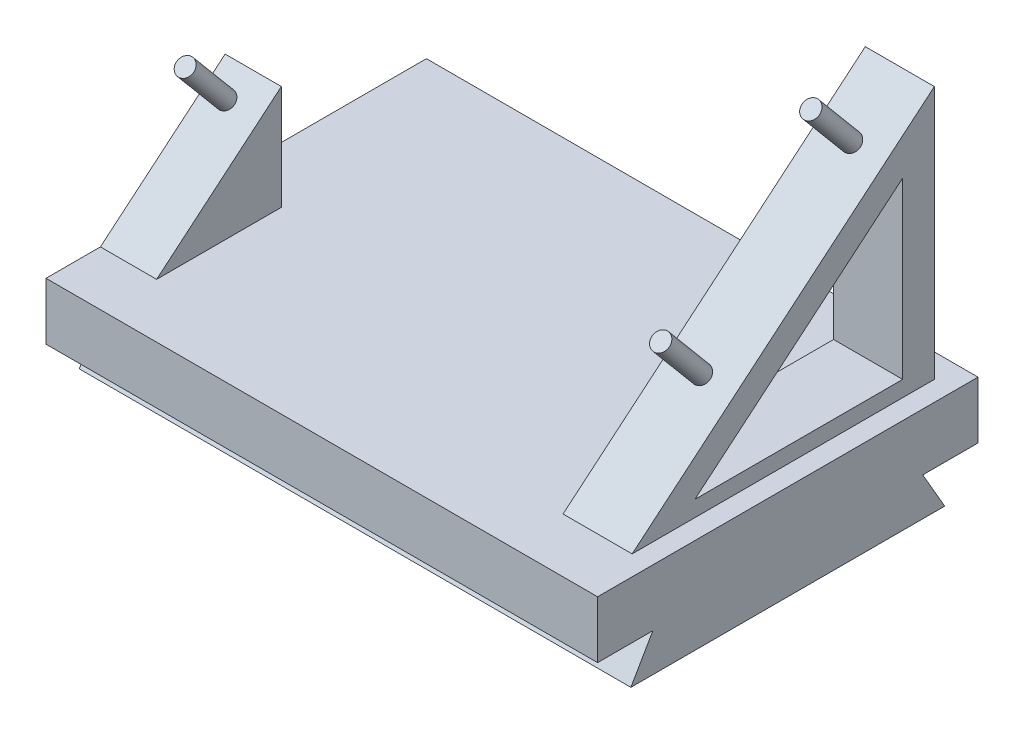
SolidWorks part; units mm, degrees
material "Plain Carbon Steel"
ref_plane "Front Plane" through (0, 0, 0) normal (0, 0, 1) x (1, 0, 0)
ref_plane "Top Plane" through (0, 0, 0) normal (0, 1, 0) x (1, 0, 0)
ref_plane "Right Plane" through (0, 0, 0) normal (1, 0, 0) x (0, 0, -1)
sketch "Sketch1" plane through (0, 0, 0) normal (0, 1, 0) x (1, 0, 0)
  line L1 (0, 0) -> (196, 0)
  line L2 (0, 0) -> (0, 150)
  line L3 (0, 150) -> (196, 150)
  line L4 (196, 0) -> (196, 150)
  dimension "D1" = 196
  dimension "D2" = 150
extrude "Boss-Extrude1" add sketch "Sketch1" along normal blind 15
sketch "Sketch2" plane through (0, 15, 0) normal (0, 1, 0) x (1, 0, 0)
  line L1 (15, 70) -> (181, 70)
  line L2 (15, 70) -> (15, 15)
  line L3 (15, 15) -> (181, 15)
  line L4 (181, 70) -> (181, 15)
  line L5 (0, 150) -> (0, 0) construction
  line L6 (0, 0) -> (196, 0) construction
  dimension "D1" = 166
  dimension "D2" = 15
  dimension "D3" = 15
  dimension "D4" = 55
extrude "Cut-Extrude1" cut sketch "Sketch2" against normal blind 9.68
sketch "Sketch3" plane through (0, 15, 0) normal (0, 1, 0) x (1, 0, 0)
  line L0 (0, 150) -> (0, 0) construction
  line L1 (181, 70) -> (15, 70) construction
  circle A0 centre (25, 133.2) radius 1.5
  circle A1 centre (23.7, 85) radius 1.5
  circle A2 centre (75.8, 118) radius 1.5
  circle A3 centre (75.8, 90.1) radius 1.5
  dimension "D1" = 3
  dimension "D2" = 3
  dimension "D3" = 3
  dimension "D4" = 3
  dimension "D5" = 15.2
  dimension "D6" = 27.9
  dimension "D7" = 5.1
  dimension "D8" = 25
  dimension "D9" = 15
  dimension "D10" = 50.8
  dimension "D11" = 1.3
extrude "Boss-Extrude2" add sketch "Sketch3" along normal blind 10
sketch "Sketch4" plane through (0, 15, 0) normal (0, 1, 0) x (1, 0, 0)
  line L0 (196, 0) -> (196, 150) construction
  line L1 (105.1, 140) -> (94.2, 140)
  line L2 (105.1, 140) -> (105.1, 76)
  line L3 (105.1, 76) -> (94.2, 76)
  line L4 (94.2, 140) -> (94.2, 76)
  line L5 (180.1, 140) -> (169.2, 140)
  line L6 (180.1, 140) -> (180.1, 76)
  line L7 (180.1, 76) -> (169.2, 76)
  line L8 (169.2, 140) -> (169.2, 76)
  line L9 (196, 150) -> (0, 150) construction
  line L11 (181, 70) -> (15, 70) construction
  dimension "D1" = 10.9
  dimension "D2" = 10.9
  dimension "D3" = 15.9
  dimension "D4" = 64.1
  dimension "D5" = 10
  dimension "D6" = 6
  dimension "D7" = 6
  dimension "D8" = 10
extrude "Boss-Extrude3" add sketch "Sketch4" along normal blind 40
sketch "Sketch5" plane through (196, 0, 0) normal (1, 0, 0) x (0, 0, -1)
  line L3 (140, 55) -> (92.3299, 15)
  line L4 (140, 55) -> (140, 15) construction
  line L5 (76, 55) -> (140, 55) construction
  line L6 (76, 15) -> (140, 15) construction
  line L7 (92.3299, 15) -> (75, 15)
  line L8 (0, 15) -> (150, 15) construction
  line L9 (75, 15) -> (75, 55)
  line L10 (75, 55) -> (140, 55)
  dimension "D1" = 140
extrude "Cut-Extrude2" cut sketch "Sketch5" against normal blind 109
sketch "Sketch6" plane through (0, -36.6612, -30.7624) normal (0, 0.766, 0.6428) x (1, 0, 0)
  line L1 (94.2, 80.3706) -> (94.2, 142.5995) construction
  line L3 (105.1, 142.5995) -> (94.2, 142.5995) construction
  circle A0 centre (174.7, 132.5995) radius 1.4
  circle A1 centre (174.7, 101.6895) radius 1.4
  circle A2 centre (99.7, 132.5995) radius 1.375
  circle A3 centre (99.7, 101.6895) radius 1.375
  dimension "D1" = 2.75
  dimension "D2" = 2.75
  dimension "D3" = 2.8
  dimension "D4" = 2.8
  dimension "D7" = 10
  dimension "D8" = 30.91
  dimension "D5" = 75
  dimension "D6" = 5.5
extrude "Boss-Extrude4" add sketch "Sketch6" along normal blind 10
fillet "Fillet1" radius 10 4 edges at (98, 15, -150) (196, 15, -75) (98, 15, 0) (0, 15, -75)
sketch "Sketch8" plane through (0, 15, 0) normal (0, 1, 0) x (1, 0, 0)
  line L0 (196, 0) -> (0, 0) construction
  line L1 (0, 150) -> (92.2324, 150)
  line L2 (0, 150) -> (0, 0)
  line L3 (0, 0) -> (92.2324, 0)
  line L4 (92.2324, 150) -> (92.2324, 0)
  line L5 (94.2, 140) -> (10, 140) construction
  line L6 (196, 0) -> (92.2324, 0)
  line L7 (196, 0) -> (196, 87.5)
  line L8 (196, 87.5) -> (92.2324, 87.5)
  line L9 (92.2324, 0) -> (92.2324, 87.5)
  line L10 (196, 150) -> (92.2324, 150)
  line L11 (196, 150) -> (196, 140)
  line L12 (196, 140) -> (92.2324, 140)
  line L13 (92.2324, 150) -> (92.2324, 140)
  line M15 (94.2, 140) -> (10, 140)
  line M16 (10, 140) -> (10, 10)
  line M17 (10, 10) -> (186, 10)
  line M18 (186, 10) -> (186, 140)
  line M19 (186, 140) -> (180.1, 140)
  circle M25 centre (75.8, 90.1) radius 1.5
  circle M26 centre (75.8, 118) radius 1.5
  circle M27 centre (23.7, 85) radius 1.5
  circle M28 centre (25, 133.2) radius 1.5
  line M29 (181, 15) -> (15, 15)
  line M30 (15, 15) -> (15, 70)
  line M31 (15, 70) -> (181, 70)
  line M32 (181, 70) -> (181, 15)
  dimension "D1" = 92.2324
  dimension "D2" = 87.5
extrude "Cut-Extrude4" cut sketch "Sketch8" against normal blind 50 and the other way blind 68 contours L4 L1 L2 L3 M17 M16 M15 | L4 M15 M16 M17 M29 M30 M31 M25 M27 M28 M26 | L4 M31 M30 M29 | L8 L4 M18 M31 M32 M29 M17 | L4 M31 M29 M32 | L7 L8 L4 L6 M18 M17 | L12 L11 L10 L4 M15 M19 region at (46.1162, 15, -148.2391) region at (144.1162, 15, -145) region at (49.4651, 15, -96.384) region at (93.5897, 15, -5) region at (139.1162, 15, -86.2835) region at (136.6162, 15, -42.5) region at (53.6162, 15, -42.5)
sketch "Sketch10" plane through (92.2324, 0, 0) normal (-1, 0, 0) x (0, 0, 1)
  line L1 (-140, 0) -> (-80, 0)
  line L2 (-140, 0) -> (-140, 37)
  line L3 (-140, 37) -> (-80, 37)
  line L4 (-80, 0) -> (-80, 37)
  dimension "D1" = 37
  dimension "D2" = 60
extrude "Cut-Extrude5" cut sketch "Sketch10" along normal blind 83
sketch "Sketch11" plane through (0, 15, 0) normal (0, 1, 0) x (1, 0, 0)
  line L1 (186, 87.5) -> (196, 87.5)
  line L2 (186, 87.5) -> (186, 140)
  line L3 (186, 140) -> (196, 140)
  line L4 (196, 87.5) -> (196, 140)
extrude "Cut-Extrude6" cut sketch "Sketch11" against normal blind 36
sketch "Sketch13" plane through (92.2324, 0, 0) normal (-1, 0, 0) x (0, 0, 1)
  line L5 (-140, 15) -> (-112, 15)
  line L6 (-140, 15) -> (-140, 57.5)
  line L7 (-140, 57.5) -> (-112, 57.5)
  line L8 (-112, 15) -> (-112, 57.5)
  dimension "D1" = 42.5
  dimension "D2" = 28
extrude "Cut-Extrude7" cut sketch "Sketch13" against normal blind 19
sketch "Sketch19" plane through (0, 0, -87.5) normal (0, 0, 1) x (1, 0, 0)
  line L2 (92.2324, 0) -> (96.2324, 0)
  line L3 (92.2324, 0) -> (92.2324, 55)
  line L4 (92.2324, 55) -> (96.2324, 55)
  line L5 (96.2324, 0) -> (96.2324, 55)
  line L6 (186, 0) -> (183.23, 0)
  line L7 (186, 0) -> (186, 50)
  line L8 (186, 50) -> (183.23, 50)
  line L9 (183.23, 0) -> (183.23, 50)
  dimension "D1" = 55
  dimension "D2" = 4
  dimension "D3" = 2.77
  dimension "D4" = 50
extrude "Cut-Extrude9" cut sketch "Sketch19" against normal blind 76
sketch "Sketch21" plane through (0, 0, -140) normal (0, 0, -1) x (-1, 0, 0)
  line L1 (-183.23, 0) -> (-96.2324, 0)
  line L2 (-183.23, 0) -> (-183.23, 15)
  line L3 (-183.23, 15) -> (-96.2324, 15)
  line L4 (-96.2324, 0) -> (-96.2324, 15)
extrude "Boss-Extrude6" add sketch "Sketch21" along normal blind 3.75
sketch "Sketch22" plane through (0, 0, -87.5) normal (0, 0, 1) x (1, 0, 0)
  line L1 (96.2324, 0) -> (183.23, 0)
  line L2 (96.2324, 0) -> (96.2324, 15)
  line L3 (96.2324, 15) -> (183.23, 15)
  line L4 (183.23, 0) -> (183.23, 15)
extrude "Boss-Extrude7" add sketch "Sketch22" along normal blind 3.75
sketch "Sketch23" plane through (96.2324, 0, 0) normal (-1, 0, 0) x (0, 0, 1)
  line L0 (-143.75, 6) -> (-135.0359, 6)
  line L1 (-143.75, 0) -> (-143.75, 15) construction
  line L2 (-135.0359, 6) -> (-138.5, 0)
  line L3 (-143.75, 0) -> (-83.75, 0) construction
  line L4 (-138.5, 0) -> (-143.75, 0)
  line L5 (-143.75, 0) -> (-143.75, 6)
  line L6 (-83.75, 0) -> (-83.75, 6)
  line L7 (-83.75, 15) -> (-83.75, 0) construction
  line L8 (-83.75, 6) -> (-92.4641, 6)
  line L9 (-92.4641, 6) -> (-89, 0)
  line L10 (-89, 0) -> (-83.75, 0)
  dimension "D1" = 60
  dimension "D2" = 60
  dimension "D3" = 5.25
  dimension "D4" = 6
  dimension "D5" = 5.25
  dimension "D6" = 6
extrude "Cut-Extrude11" cut sketch "Sketch23" against normal blind 94.75
sketch "Sketch24" plane through (180.1, 0, 0) normal (1, 0, 0) x (0, 0, -1)
  line L0 (135, 45) -> (102.2268, 17.5)
  line L1 (102.2268, 17.5) -> (135, 17.5)
  line L2 (135, 17.5) -> (135, 45)
  line L3 (140, 55) -> (140, 15) construction
  line L4 (83.75, 15) -> (143.75, 15) construction
  dimension "D1" = 5
  dimension "D2" = 2.5
  dimension "D3" = 40
  dimension "D4" = 10
extrude "Cut-Extrude12" cut sketch "Sketch24" against normal blind 16
sketch "Sketch25" plane through (96.2324, 0, 0) normal (-1, 0, 0) x (0, 0, 1)
  line L0 (-127.7265, 12) -> (-133.5, 2)
  line L1 (-133.5, 2) -> (-94, 2)
  line L2 (-94, 2) -> (-99.7735, 12)
  line L3 (-99.7735, 12) -> (-127.7265, 12)
  line L4 (-138.5, 0) -> (-89, 0) construction
  dimension "D1" = 60
  dimension "D2" = 60
  dimension "D3" = 2
  dimension "D4" = 10
  dimension "D5" = 5
  dimension "D6" = 5
